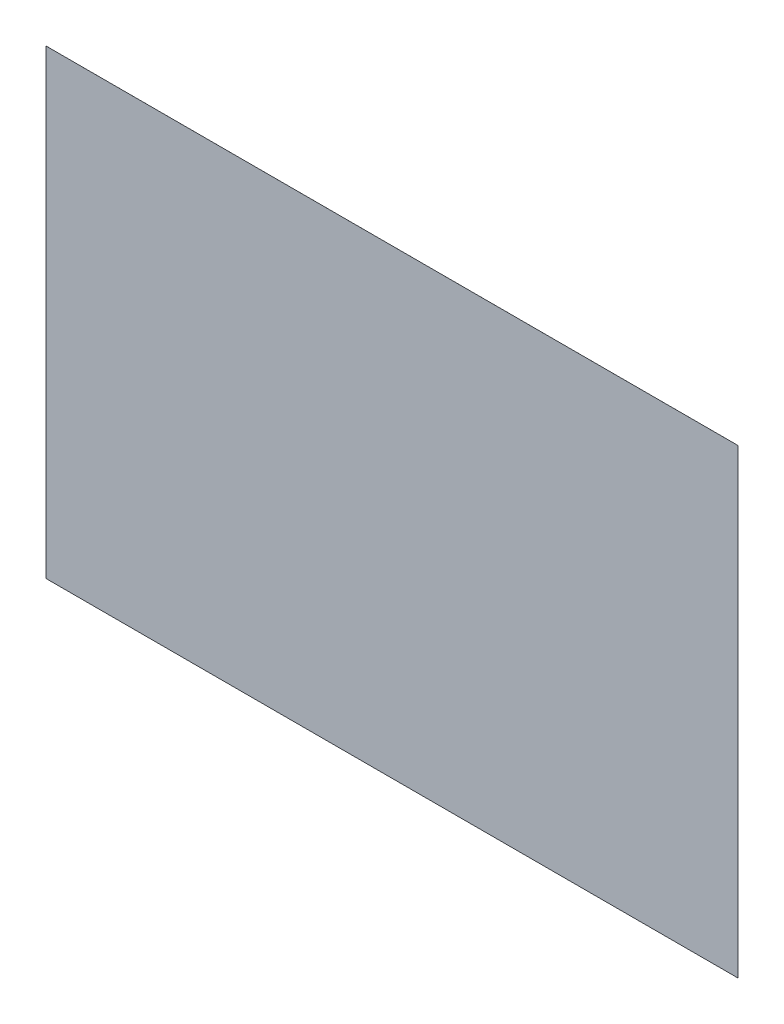
SolidWorks part; units mm, degrees
ref_plane "前视基准面" through (0, 0, 0) normal (0, 0, 1) x (1, 0, 0)
ref_plane "上视基准面" through (0, 0, 0) normal (0, 1, 0) x (1, 0, 0)
ref_plane "右视基准面" through (0, 0, 0) normal (1, 0, 0) x (0, 0, -1)
other "Configuration Table"
sketch "草图1" plane through (0, 0, 0) normal (0, 0, 1) x (1, 0, 0)
  line L1 (0, 0) -> (60000, 0)
  line L2 (0, 0) -> (0, 40000)
  line L3 (0, 40000) -> (60000, 40000)
  line L4 (60000, 0) -> (60000, 40000)
base flange "基体-法兰1" sketch "草图1" thickness 1 reverse thickness direction no parameters "D1"=1
sketch "折弯-线1" plane through (0, 0, 0) normal (0, 1, 0) x (1, 0, 0)
sketch "边界框1" plane through (0, 0, 0) normal (0, 1, 0) x (1, 0, 0)
sheet metal parameters "钣金6" thickness 1 parameters "D1"=1
flat pattern "平展型式6" [suppressed]
sketch "折弯-线2" plane through (0, 0, 0) normal (0, 1, 0) x (1, 0, 0)
sketch "边界框2" [suppressed] plane through (0, 0, 0) normal (0, 1, 0) x (1, 0, 0)
